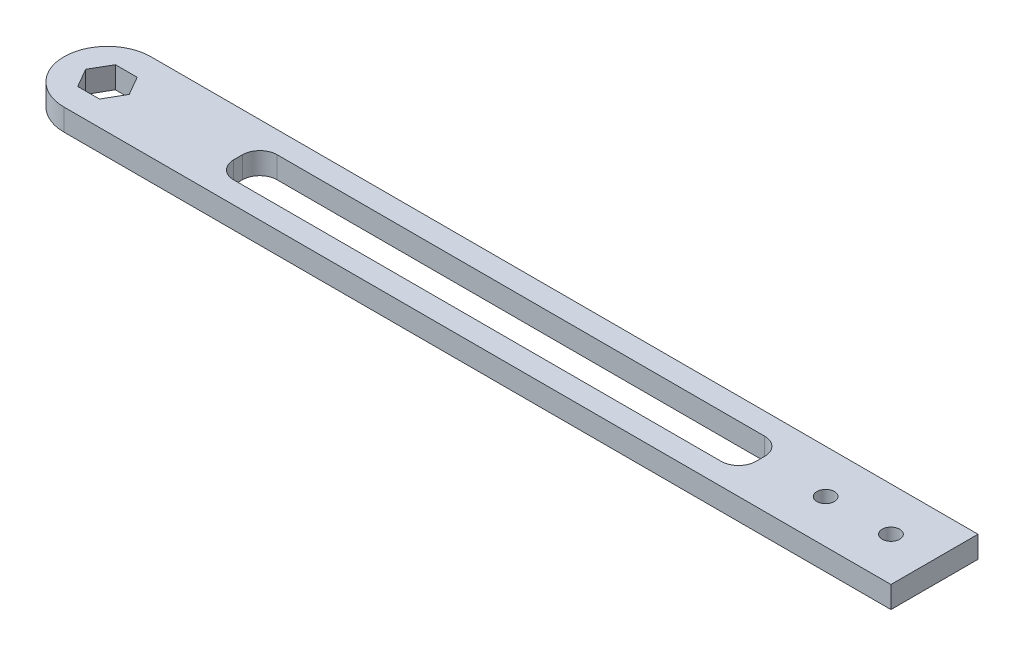
SolidWorks part; units mm, degrees
material "5052-O"
ref_plane "Front Plane" through (0, 0, 0) normal (0, 0, 1) x (1, 0, 0)
ref_plane "Top Plane" through (0, 0, 0) normal (0, 1, 0) x (1, 0, 0)
ref_plane "Right Plane" through (0, 0, 0) normal (1, 0, 0) x (0, 0, -1)
sketch "Sketch1" plane through (0, 0, 0) normal (0, 1, 0) x (1, 0, 0)
  line L1 (-127, -12.7) -> (127, -12.7)
  line L2 (-127, -12.7) -> (-127, 12.7)
  line L3 (-127, 12.7) -> (127, 12.7)
  line L4 (127, -12.7) -> (127, 12.7)
  line L5 (-127, -12.7) -> (127, 12.7) construction
  line L6 (-127, 12.7) -> (127, -12.7) construction
  point P0 (0, 0)
  dimension "D1" = 25.4
  dimension "D2" = 254
extrude "Boss-Extrude1" add sketch "Sketch1" along normal mid plane 6.35
fillet "Fillet1" radius 12.7 2 edges at (-127, 0, -12.7) (-127, 0, 12.7)
sketch "Sketch2" plane through (0, 3.175, 0) normal (0, 1, 0) x (1, 0, 0)
  line L0 (0, -36.7292) -> (0, 36.7292) construction
  line L1 (114.3, 0) -> (-114.3, 0) construction
  point P1 (95.25, 0)
  point P10 (0, 0)
  point P11 (0, 0)
  dimension "D1" = 12.7
  dimension "D2" = 19.05
hole_wizard "#10 Clearance Hole1" positions "Sketch5" profile "Sketch7" hole size "#10" standard "ANSI Inch" end condition through all
sketch "Sketch5" plane through (0, 3.175, 0) normal (0, 1, 0) x (1, 0, 0)
  point P0 (114.3, 0)
  point P3 (95.25, 0)
sketch "Sketch7" plane through (114.3, 3.175, 0) normal (1, 0, 0) x (0, 0, 1)
  line L0 (0, 0) -> (0, 6.35)
  line L1 (0, 6.35) -> (2.5527, 6.35)
  line L2 (2.5527, 6.35) -> (2.5527, 0)
  line L5 (2.5527, 0) -> (0, 0)
  line L11 (0, -6.35) -> (0, 107.95) construction
  dimension "Thru Hole Dia." = 5.1054
  dimension "Thru Hole Depth" = 6.35
sketch "Sketch9" plane through (0, 3.175, 0) normal (0, 1, 0) x (1, 0, 0)
  line L0 (127, 12.7) -> (-114.3, 12.7) construction
  line L1 (-76.2, -6.35) -> (76.2, -6.35)
  line L2 (-76.2, -6.35) -> (-76.2, 6.35)
  line L3 (-76.2, 6.35) -> (76.2, 6.35)
  line L4 (76.2, -6.35) -> (76.2, 6.35)
  line L5 (-76.2, -6.35) -> (76.2, 6.35) construction
  line L6 (-76.2, 6.35) -> (76.2, -6.35) construction
  point P0 (0, 0)
  dimension "D1" = 50.8
  dimension "D2" = 6.35
extrude "Cut-Extrude2" cut sketch "Sketch9" against normal through all
fillet "Fillet2" radius 5.08 4 edges at (-76.2, 0, -6.35) (-76.2, 0, 6.35) (76.2, 0, 6.35) (76.2, 0, -6.35)
sketch "Sketch10" plane through (0, -3.175, 0) normal (0, -1, 0) x (1, 0, 0)
  line L1 (-111.125, 5.4993) -> (-117.475, 5.4993)
  line L2 (-117.475, 5.4993) -> (-120.65, 0)
  line L3 (-120.65, 0) -> (-117.475, -5.4993)
  line L4 (-117.475, -5.4993) -> (-111.125, -5.4993)
  line L5 (-111.125, -5.4993) -> (-107.95, 0)
  line L6 (-107.95, 0) -> (-111.125, 5.4993)
  circle A0 centre (-114.3, 0) radius 5.4993 construction
  arc A1 (-114.3, 12.7) -> (-127, 0) centre (-114.3, 0) ccw construction
  point P1 (0, 0)
  dimension "D1" = 12.7
extrude "Cut-Extrude3" cut sketch "Sketch10" against normal through all
